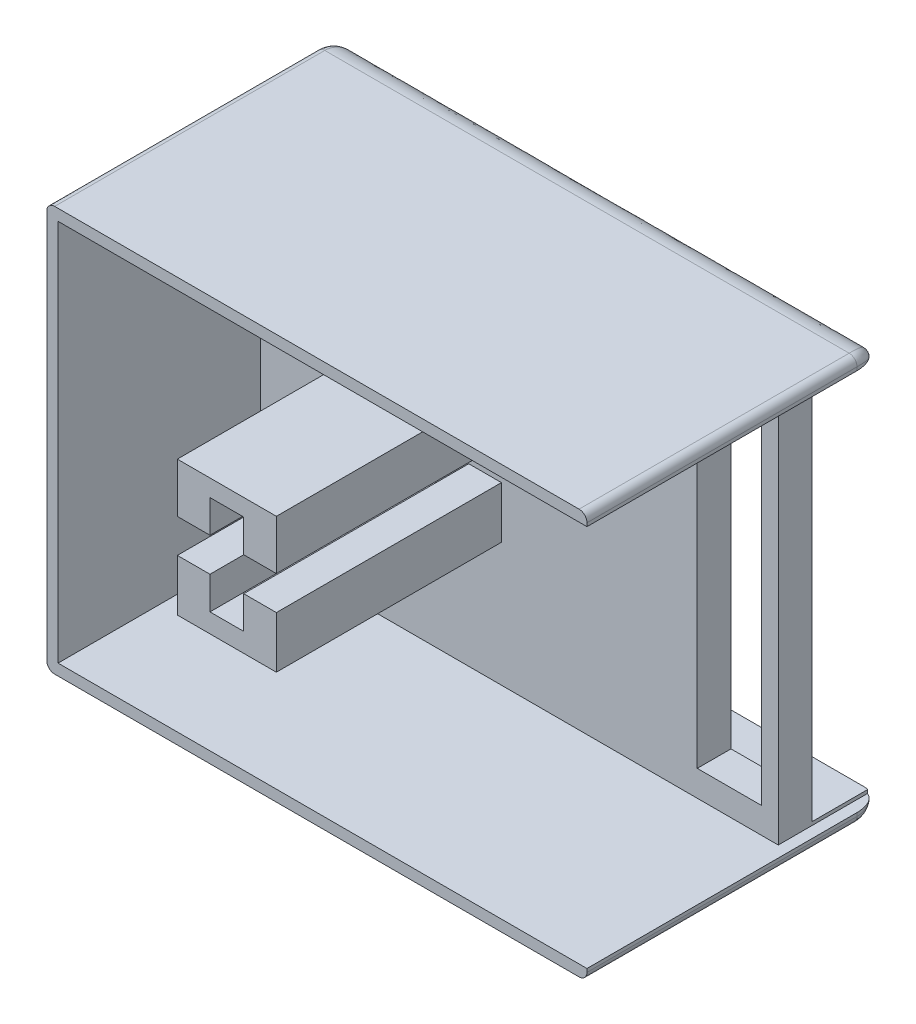
SolidWorks part; units mm, degrees
ref_plane "Front Plane" through (0, 0, 0) normal (0, 0, 1) x (1, 0, 0)
ref_plane "Top Plane" through (0, 0, 0) normal (0, 1, 0) x (1, 0, 0)
ref_plane "Right Plane" through (0, 0, 0) normal (1, 0, 0) x (0, 0, -1)
sketch "Sketch1" plane through (0, 0, 0) normal (0, 0, 1) x (1, 0, 0)
  line L1 (-12, -9) -> (12, -9)
  line L2 (-12, -9) -> (-12, 9)
  line L3 (-12, 9) -> (12, 9)
  line L4 (12, -9) -> (12, 9)
  line L5 (-12, -9) -> (12, 9) construction
  line L6 (-12, 9) -> (12, -9) construction
  point P0 (0, 0)
  dimension "D1" = 24
  dimension "D2" = 18
extrude "Boss-Extrude1" add sketch "Sketch1" along normal blind 13
fillet "Fillet1" radius 0.65 4 edges at (-12, 0, 0) (0, -9, 0) (12, 0, 0) (0, 9, 0) second distance 1 first distance on face at (0, 0, 0)
fillet "Fillet2" radius 0.35 8 edges
sketch "Sketch2" plane through (0, 0, 13) normal (0, 0, 1) x (1, 0, 0)
  line L0 (-11.65, -9) -> (11.65, -9) construction
  line L1 (11.5, 8.5) -> (-11.5, 8.5)
  line L2 (11.5, 8.5) -> (11.5, -8.5)
  line L3 (11.5, -8.5) -> (-11.5, -8.5)
  line L4 (-11.5, 8.5) -> (-11.5, -8.5)
  line L5 (12, -8.65) -> (12, 8.65) construction
  line L6 (11.65, 9) -> (-11.65, 9) construction
  line L7 (-12, 8.65) -> (-12, -8.65) construction
  dimension "D1" = 0.5
  dimension "D2" = 0.5
  dimension "D3" = 0.5
  dimension "D4" = 0.5
extrude "Cut-Extrude1" cut sketch "Sketch2" against normal blind 9
sketch "Sketch11" plane through (0, 0, 4) normal (0, 0, 1) x (1, 0, 0)
  line L1 (-5.2, -3) -> (-0.8, -3)
  line L2 (-5.2, -3) -> (-5.2, 3)
  line L3 (-5.2, 3) -> (-0.8, 3)
  line L4 (-0.8, -3) -> (-0.8, 3)
  line L5 (-5.2, -3) -> (-0.8, 3) construction
  line L6 (-5.2, 3) -> (-0.8, -3) construction
  line L7 (-11.5, 8.5) -> (-11.5, -8.5) construction
  point P0 (0, 0)
  dimension "D1" = 6
  dimension "D2" = 4.4
  dimension "D3" = 6.3
extrude "Boss-Extrude4" add sketch "Sketch11" along normal blind 10
sketch "Sketch12" plane through (0, 0, 14) normal (0, 0, 1) x (1, 0, 0)
  line L0 (-5.2, 3) -> (-5.2, -3) construction
  line L1 (-0.8, 0.7955) -> (-5.2, 0.7955)
  line L2 (-0.8, 0.7955) -> (-0.8, -0.7045)
  line L3 (-0.8, -0.7045) -> (-5.2, -0.7045)
  line L4 (-5.2, 0.7955) -> (-5.2, -0.7045)
  line L5 (-0.8, 0.7955) -> (-5.2, -0.7045) construction
  line L6 (-0.8, -0.7045) -> (-5.2, 0.7955) construction
  point P0 (-3, 0.0455)
  dimension "D1" = 1.5
extrude "Cut-Extrude6" cut sketch "Sketch12" against normal blind 10
sketch "Sketch13" plane through (0, 0, 14) normal (0, 0, 1) x (1, 0, 0)
  line L0 (-5.2, 0.7955) -> (-5.2, -0.7045) construction
  line L1 (-3.75, -2.1545) -> (-2.25, -2.1545)
  line L2 (-3.75, -2.1545) -> (-3.75, 2.2455)
  line L3 (-3.75, 2.2455) -> (-2.25, 2.2455)
  line L4 (-2.25, -2.1545) -> (-2.25, 2.2455)
  line L5 (-3.75, -2.1545) -> (-2.25, 2.2455) construction
  line L6 (-3.75, 2.2455) -> (-2.25, -2.1545) construction
  line L7 (-0.8, 0.7955) -> (-5.2, 0.7955) construction
  point P0 (-3, 0.0455)
extrude "Cut-Extrude7" cut sketch "Sketch13" against normal blind 10
sketch "Sketch14" plane through (0, 0, 13) normal (0, 0, 1) x (1, 0, 0)
  line L0 (12, -8.65) -> (12, 8.65) construction
  line L1 (11.5, 8.5) -> (12, 8.5)
  line L2 (11.5, 8.5) -> (11.5, -8.5)
  line L3 (11.5, -8.5) -> (12, -8.5)
  line L4 (12, 8.5) -> (12, -8.5)
extrude "Cut-Extrude8" cut sketch "Sketch14" against normal through all
sketch "Sketch17" plane through (0, 0, 0) normal (0, 0, -1) x (-1, 0, 0)
  line L0 (-11.35, -8.35) -> (11.35, -8.35) construction
  line L1 (-11.35, 8.35) -> (6.65, 8.35)
  line L2 (-11.35, 8.35) -> (-11.35, -8.35)
  line L3 (-11.35, -8.35) -> (6.65, -8.35)
  line L4 (6.65, 8.35) -> (6.65, -8.35)
  dimension "D1" = 18
extrude "Cut-Extrude9" cut sketch "Sketch17" against normal blind 2.5
sketch "Sketch18" plane through (11.35, 0, 0) normal (-1, 0, 0) x (0, 0, 1)
  line L0 (2.5, 8.35) -> (2.5, -8.35) construction
  line L1 (0, 8.35) -> (2.5, 8.35)
  line L2 (0, 8.35) -> (0, -8.35)
  line L3 (0, -8.35) -> (2.5, -8.35)
  line L4 (2.5, 8.35) -> (2.5, -8.35)
extrude "Cut-Extrude10" cut sketch "Sketch18" against normal through all
sketch "Sketch19" plane through (0, 0, 2.5) normal (0, 0, -1) x (-1, 0, 0)
  line L0 (6.65, 8.35) -> (-11.5, 8.35) construction
  line L1 (-10.75, -7.35) -> (-7.9, -7.35)
  line L2 (-10.75, -7.35) -> (-10.75, 7.35)
  line L3 (-10.75, 7.35) -> (-7.9, 7.35)
  line L4 (-7.9, -7.35) -> (-7.9, 7.35)
  line L5 (-10.75, -7.35) -> (-7.9, 7.35) construction
  line L6 (-10.75, 7.35) -> (-7.9, -7.35) construction
  line L7 (-11.5, -8.35) -> (6.65, -8.35) construction
  line L8 (-11.5, -8.35) -> (-11.5, 8.35) construction
  point P0 (-7.9369, 0)
  dimension "D1" = 1
  dimension "D2" = 1
  dimension "D3" = 2.85
  dimension "D4" = 0.75
extrude "Cut-Extrude11" cut sketch "Sketch19" against normal through all
